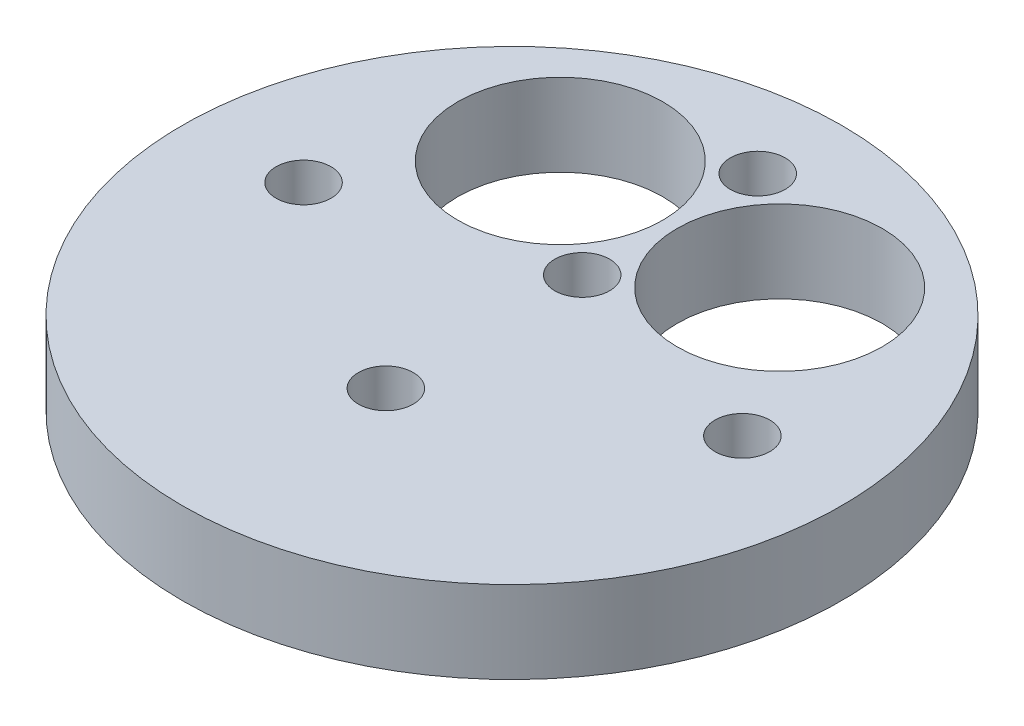
SolidWorks part; units mm, degrees
material "G10 Fiberglass"
ref_plane "Front Plane" through (0, 0, 0) normal (0, 0, 1) x (1, 0, 0)
ref_plane "Top Plane" through (0, 0, 0) normal (0, 1, 0) x (1, 0, 0)
ref_plane "Right Plane" through (0, 0, 0) normal (1, 0, 0) x (0, 0, -1)
ref_axis "Axis1" through (0, 55, 0) along (0, -1, 0)
sketch "Sketch1" plane through (0, 0, 0) normal (0, 0, 1) x (1, 0, 0)
  line L0 (0, 0) -> (38.1508, 0)
  line L3 (38.1508, 0) -> (38.1508, 9.525)
  line L4 (38.1508, 9.525) -> (0, 9.525)
  line L5 (0, 55) -> (0, -55) construction
  line L6 (0, 9.525) -> (0, 0)
  line L7 (0, 0) -> (0, 21.2966) construction
  dimension "D1" = 76.3016
  dimension "D2" = 9.525
revolve "Revolve1" add sketch "Sketch1" angle 360 about L7
sketch "Sketch2" plane through (0, 9.525, 0) normal (0, 1, 0) x (1, 0, 0)
  line L0 (-12.7, 18.288) -> (12.7, 18.288) construction
  line L1 (0, 28.448) -> (0, 8.128) construction
  line L2 (-12.7, 18.288) -> (12.7, 18.288) construction
  line L3 (-12.7, 32.258) -> (12.7, 32.258) construction
  line L4 (-12.7, 4.318) -> (12.7, 4.318) construction
  circle A0 centre (-12.7, 18.288) radius 11.8745
  circle A1 centre (0, 0) radius 38.1508
  circle A3 centre (12.7, 18.288) radius 11.8745
  circle A4 centre (0, 28.448) radius 3.175
  circle A5 centre (0, 8.128) radius 3.175
  arc A6 (-12.7, 32.258) -> (-12.7, 4.318) centre (-12.7, 18.288) ccw construction
  arc A7 (12.7, 4.318) -> (12.7, 32.258) centre (12.7, 18.288) ccw construction
  circle A8 centre (0, -14.605) radius 3.175
  circle A9 centre (0, 0) radius 34.163 construction
  circle A11 centre (0, 0) radius 38.1508 construction
  point P11 (0, 18.288)
  point P12 (0, 18.288)
  point P15 (0, 18.288)
  dimension "D2" = 23.749
  dimension "D3" = 23.749
  dimension "D5" = 6.35
  dimension "D6" = 6.35
  dimension "D11" = 6.35
  dimension "D4" = 25.4
  dimension "D7" = 20.32
  dimension "D8" = 25.4
  dimension "D9" = 27.94
  dimension "D10" = 14.605
  dimension "D12" = 4.318
  dimension "D1" = 0
extrude "Cut-Extrude1" cut sketch "Sketch2" against normal through all both and the other way through all
sketch "Sketch3" plane through (0, 9.525, 0) normal (0, 1, 0) x (1, 0, 0)
  circle A0 centre (-25.4, 1.27) radius 3.175
  circle A1 centre (25.4, 1.27) radius 3.175
  dimension "D1" = 6.35
  dimension "D2" = 6.35
  dimension "D3" = 50.8
  dimension "D4" = 1.27
extrude "Cut-Extrude2" cut sketch "Sketch3" against normal through all both
ref_plane "Plane1" through (0, 4.7625, 0) normal (0, 1, 0) x (-1, 0, 0)
equation "\"D3@Sketch2\"=\"D2@Sketch2\""
equation "\"D6@Sketch2\"=\"D5@Sketch2\""
